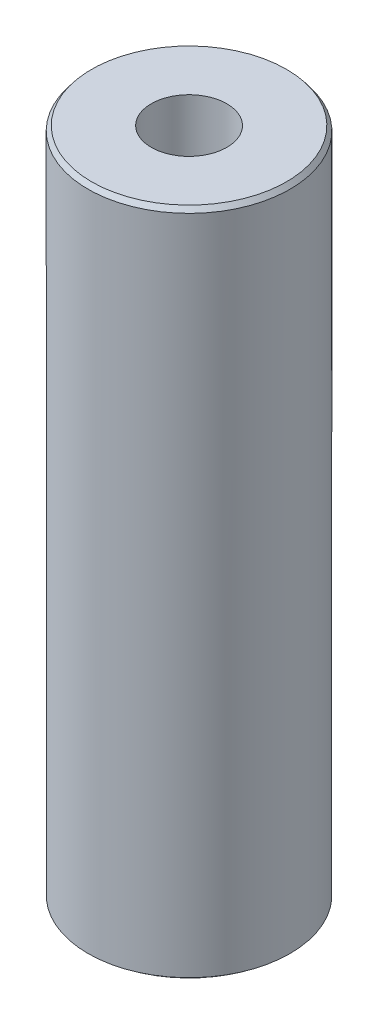
SolidWorks part; units mm, degrees
ref_plane "Front Plane" through (0, 0, 0) normal (0, 0, 1) x (1, 0, 0)
ref_plane "Top Plane" through (0, 0, 0) normal (0, 1, 0) x (1, 0, 0)
ref_plane "Right Plane" through (0, 0, 0) normal (1, 0, 0) x (0, 0, -1)
sketch "Sketch1" plane through (0, 0, 0) normal (0, 1, 0) x (1, 0, 0)
  circle A0 centre (0, 0) radius 45
  dimension "SHAFT_OD" = 90
extrude "Boss-Extrude1" add sketch "Sketch1" along normal blind 298.5531
sketch "Sketch2" plane through (0, 0, 0) normal (0, 1, 0) x (1, 0, 0)
  circle A0 centre (0, 0) radius 16.8478
  dimension "BORE_D" = 33.6956
extrude "Cut-Extrude1" cut sketch "Sketch2" along normal through all
chamfer "Chamfer1" distance 2.0714 angle 37.301 2 edges at (0, 298.5531, 45) (0, 0, 45) first distance on face at (0, 298.5531, 45) first distance on face at (0, 0, 16.8478)
